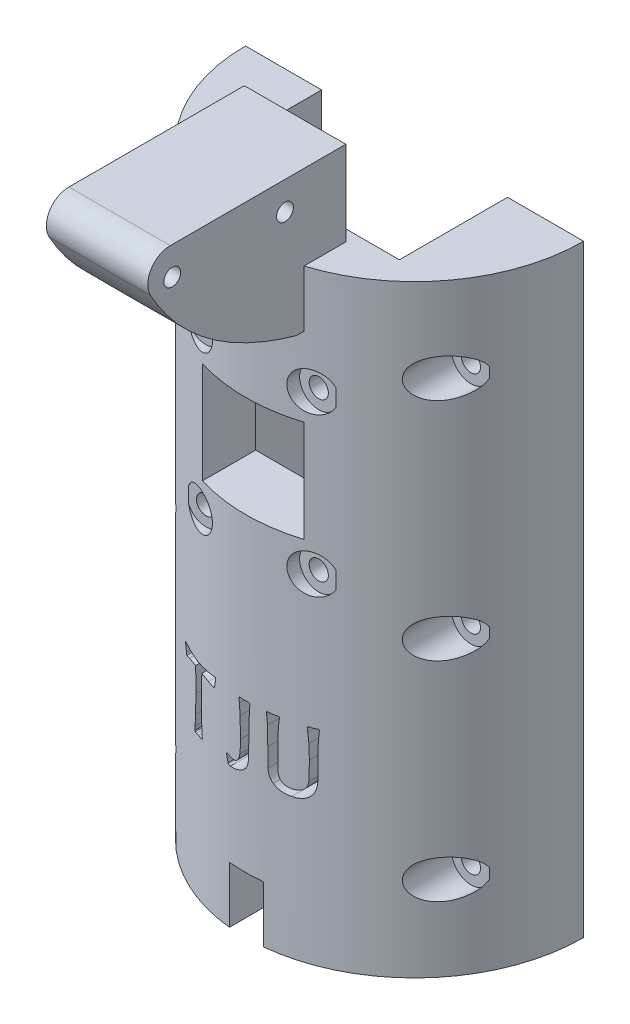
SolidWorks part; units mm, degrees
ref_plane "前视基准面" through (0, 0, 0) normal (0, 0, 1) x (1, 0, 0)
ref_plane "上视基准面" through (0, 0, 0) normal (0, 1, 0) x (1, 0, 0)
ref_plane "右视基准面" through (0, 0, 0) normal (1, 0, 0) x (0, 0, -1)
sketch "草图1" plane through (0, 0, 0) normal (0, 1, 0) x (1, 0, 0)
  line L0 (-30, 0) -> (30, 0)
  line L6 (15, 19.2) -> (-15, 19.2)
  line L7 (15, 19.2) -> (15, -19.2)
  line L8 (15, -19.2) -> (-15, -19.2)
  line L9 (-15, 19.2) -> (-15, -19.2)
  line L10 (15, 19.2) -> (-15, -19.2) construction
  line L11 (15, -19.2) -> (-15, 19.2) construction
  arc A0 (-30, 0) -> (30, 0) centre (0, 0) ccw
  point P0 (0, 0)
  dimension "D3" = 38.4
  dimension "D1" = 30
  dimension "D2" = 60
extrude "凸台-拉伸1" add sketch "草图1" along normal blind 80 contours L0 A0 L8 region at (-22.5, 0, 0.6708)
sketch "草图2" plane through (0, 0, 0) normal (0, 0, 1) x (1, 0, 0)
  line L0 (0, 122.0673) -> (0, -16.729) construction
  line L2 (-30, 0) -> (-15, 0) construction
  circle A0 centre (-10, 33) radius 1.7
  circle A1 centre (-10, 61) radius 1.7
  circle A2 centre (10, 33) radius 1.7
  circle A3 centre (10, 61) radius 1.7
  dimension "D1" = 20
  dimension "D2" = 20
  dimension "D3" = 33
  dimension "D4" = 28
extrude "切除-拉伸1" cut sketch "草图2" along normal blind 100
sketch "草图3" plane through (0, 0, 0) normal (0, 0, -1) x (-1, 0, 0)
  line L0 (-40.9161, 45) -> (57.667, 45) construction
  line L1 (-30, 80) -> (-30, 0) construction
  line L2 (30, 80) -> (30, 0) construction
  line L4 (-15, 80) -> (-30, 80) construction
  circle A0 centre (23.5, 65) radius 1.7
  circle A1 centre (-23.5, 65) radius 1.7
  circle A2 centre (23.5, 25) radius 1.7
  circle A3 centre (-23.5, 25) radius 1.7
  dimension "D1" = 40
  dimension "D2" = 40
  dimension "D3" = 6.5
  dimension "D4" = 6.5
  dimension "D5" = 15
extrude "切除-拉伸2" cut sketch "草图3" against normal blind 100
ref_plane "基准面1" through (0, 0, 40) normal (0, 0, -1) x (-1, 0, 0)
sketch "草图4" plane through (0, 0, 40) normal (0, 0, -1) x (-1, 0, 0)
  circle A0 centre (-23.5, 65) radius 3.4
  circle A1 centre (-23.5, 25) radius 3.4
  circle A2 centre (23.5, 65) radius 3.4
  circle A3 centre (23.5, 25) radius 3.4
extrude "切除-拉伸3" cut sketch "草图4" along normal blind 26.5
sketch "草图5" plane through (0, 0, 40) normal (0, 0, -1) x (-1, 0, 0)
  circle A0 centre (-10, 61) radius 3.4
  circle A1 centre (10, 61) radius 3.4
  circle A2 centre (-10, 33) radius 3.4
  circle A3 centre (10, 33) radius 3.4
extrude "切除-拉伸4" cut sketch "草图5" along normal blind 13 contours A2 | A3 | A1 | A0 region at (10, 61, 40) region at (-10, 61, 40) region at (10, 33, 40) region at (-10, 33, 40)
sketch "草图6" plane through (0, 0, 0) normal (0, -1, 0) x (1, 0, 0)
  line L0 (-30, 0) -> (30, 0)
  arc A0 (30, 0) -> (-30, 0) centre (0, 0) ccw
extrude "凸台-拉伸2" add sketch "草图6" along normal blind 3
sketch "草图7" plane through (0, -3, 0) normal (0, -1, 0) x (1, 0, 0)
  line L0 (-30, 0) -> (30, 0) construction
  line L1 (-6, 0) -> (6, 0)
  arc A0 (6, 0) -> (-6, 0) centre (0, 0) ccw
  dimension "D1" = 6
extrude "凸台-拉伸3" [suppressed] add sketch "草图7" along normal blind 9.5
sketch "草图8" plane through (0, 80, 0) normal (0, 1, 0) x (1, 0, 0)
  line L0 (0, 0) -> (0, -36.28) construction
  line L1 (-15, 0) -> (15, 0) construction
  line L2 (-7, -19.2) -> (7, -19.2)
  line L3 (15, -19.2) -> (-15, -19.2) construction
  line L4 (7, -19.2) -> (7, -29.1719)
  line L5 (-7, -19.2) -> (-7, -29.1719)
  arc A0 (-30, 0) -> (30, 0) centre (0, 0) ccw construction
  arc A1 (-7, -29.1719) -> (7, -29.1719) centre (0, 0) ccw
  point P8 (0, -19.2)
  dimension "D1" = 14
ref_plane "基准面2" through (0, 100, 0) normal (0, 1, 0) x (1, 0, 0)
sketch "草图9" plane through (0, 100, 0) normal (0, 1, 0) x (1, 0, 0)
  line L0 (0, 0) -> (0, -36.28) construction
  line L2 (-7, -19.2) -> (7, -19.2)
  line L3 (-7, -19.2) -> (-7, -64.2)
  line L4 (-7, -64.2) -> (7, -64.2)
  line L5 (7, -19.2) -> (7, -64.2)
  dimension "D1" = 14
  dimension "D2" = 45
ref_plane "基准面3" through (0, 70, 0) normal (0, 1, 0) x (1, 0, 0)
sketch "草图10" plane through (0, 70, 0) normal (0, 1, 0) x (1, 0, 0)
  line L0 (-15, 0) -> (15, 0) construction
  line L1 (-7, -29.1719) -> (-7, -19.2)
  line L2 (-7, -19.2) -> (7, -19.2)
  line L3 (7, -19.2) -> (7, -29.1719)
  arc A0 (-7, -29.1719) -> (7, -29.1719) centre (0, 0) ccw
sketch "草图13" plane through (0, 0, 0) normal (1, 0, 0) x (0, 0, -1)
  line L0 (-19.2, 100) -> (-60, 100)
  line L1 (-19.2, 100) -> (-64.2, 100) construction
  line L2 (-19.2, 100) -> (-64.2, 100) construction
  line L3 (-19.2, 100) -> (-19.2, 70)
  line L4 (-19.2, 70) -> (-29.1719, 70) construction
  line L5 (-29.1719, 70) -> (-19.2, 70) construction
  line L6 (-19.2, 70) -> (-30, 70)
  line L7 (-29.1719, 70) -> (-30, 70) construction
  line L8 (-30, 80) -> (-30, -3) construction
  line L9 (0, 80) -> (0, 0) construction
  spline S0 degree 2 poles (-60, 100) (-54.4581, 76.8596) (-30, 70) knots 0 0 0 1 1 1
  dimension "D1" = 19.2
extrude "凸台-拉伸4" add sketch "草图13" along normal mid plane 18
sketch "草图14" plane through (-9, 0, 0) normal (-1, 0, 0) x (0, 0, 1)
  line L0 (0, 80) -> (0, -3) construction
  line L1 (19.2, 100) -> (60, 100) construction
  circle A0 centre (32, 90) radius 1.5
  circle A1 centre (52, 90) radius 1.5
  dimension "D1" = 20
  dimension "D2" = 32
  dimension "D3" = 10
  dimension "D4" = 10
extrude "切除-拉伸6" cut sketch "草图14" against normal blind 18
sketch "草图17" plane through (0, 0, 0) normal (1, 0, 0) x (0, 0, -1)
  line L0 (0, 80) -> (0, -3) construction
  line L1 (-30, -3) -> (0, -3) construction
  circle A0 centre (0, 29) radius 3
  circle A1 centre (0, 49) radius 3
  dimension "D1" = 6
  dimension "D2" = 32
  dimension "D3" = 2
sketch "草图18" plane through (0, 100, 0) normal (0, 1, 0) x (1, 0, 0)
  line L0 (9, -19.2) -> (9, -60) construction
  line L1 (-9, -19.2) -> (9, -19.2)
  line L2 (-9, -19.2) -> (-9, -21.2)
  line L3 (-9, -21.2) -> (9, -21.2)
  line L4 (9, -19.2) -> (9, -21.2)
  dimension "D1" = 2
extrude "切除-拉伸9" cut sketch "草图18" against normal blind 20
sketch "草图19" plane through (0, 0, 0) normal (0, 1, 0) x (1, 0, 0)
  circle A0 centre (0, 0) radius 3
extrude "切除-拉伸10" [suppressed] cut sketch "草图19" against normal blind 3
ref_plane "基准面4" through (0, 16, 0) normal (0, 1, 0) x (1, 0, 0)
fillet "圆角4" [suppressed] radius 1
chamfer "倒角2" [suppressed] distance 2 angle 45
sketch "草图20" plane through (0, -3, 0) normal (0, -1, 0) x (1, 0, 0)
  line L0 (-30, 0) -> (30, 0) construction
  circle A0 centre (0, 20.5) radius 6
  dimension "D1" = 12
  dimension "D2" = 20.5
extrude "切除-拉伸11" [suppressed] cut sketch "草图20" against normal blind 15
sketch "草图23" [suppressed] plane through (0, 0, 19.2) normal (0, 0, -1) x (-1, 0, 0)
  line L1 (-5.8575, 12) -> (2.8125, 12)
  line L2 (-5.8575, 12) -> (-5.8575, -3.4639)
  line L3 (-5.8575, -3.4639) -> (2.8125, -3.4639)
  line L4 (2.8125, 12) -> (2.8125, -3.4639)
extrude "切除-拉伸14" [suppressed] cut sketch "草图23" against normal blind 30
sketch "草图25" plane through (0, 100, 0) normal (0, 1, 0) x (1, 0, 0)
  line L1 (-9, -21.2) -> (9, -21.2)
  line L2 (-9, -21.2) -> (-9, -60)
  line L3 (-9, -60) -> (9, -60)
  line L4 (9, -21.2) -> (9, -60)
extrude "切除-拉伸16" cut sketch "草图25" against normal blind 5
fillet "圆角6" radius 4 1 edges at (0, 95, 58.5139)
sketch "草图28" plane through (0, -3, 0) normal (0, -1, 0) x (1, 0, 0)
  line L5 (-30, 0) -> (30, 0)
  line L8 (-30, 0) -> (30, 0)
  arc A4 (30, 0) -> (-30, 0) centre (0, 0) ccw
  arc A7 (30, 0) -> (-30, 0) centre (0, 0) ccw
  dimension "D1" = 0
extrude "凸台-拉伸7" add sketch "草图28" along normal blind 19
sketch "草图26" [suppressed] plane through (0, -3, 0) normal (0, -1, 0) x (1, 0, 0)
  line L0 (-2.8125, 25.8) -> (-2.8125, 29.8679)
  line L1 (5.8575, 29.4226) -> (5.8575, 21.8)
  line L2 (-30, 0) -> (30, 0)
  arc A2 (-2.8125, 25.8) -> (5.8575, 21.8) centre (0, 20.5) ccw
  arc A3 (6, 0) -> (-6, 0) centre (0, 0) ccw
  arc A4 (30, 0) -> (-30, 0) centre (0, 0) ccw
extrude "凸台-拉伸5" [suppressed] add sketch "草图26" along normal blind 2
sketch "草图27" [suppressed] plane through (0, -12.5, 0) normal (0, -1, 0) x (1, 0, 0)
  line L0 (-6, 0) -> (6, 0)
  arc A0 (6, 0) -> (-6, 0) centre (0, 0) ccw
extrude "凸台-拉伸6" [suppressed] add sketch "草图27" along normal blind 2
sketch "草图29" plane through (0, 0, 0) normal (0, 1, 0) x (1, 0, 0)
  line L1 (15, -19.2) -> (-15, -19.2)
  line L2 (15, -19.2) -> (15, 0)
  line L3 (15, 0) -> (-15, 0)
  line L4 (-15, -19.2) -> (-15, 0)
extrude "切除-拉伸17" cut sketch "草图29" against normal up to next
sketch "草图30" plane through (0, -22, 0) normal (0, -1, 0) x (1, 0, 0)
  line L0 (30, 0) -> (-30, 0)
  line L5 (15, 19.2) -> (15, 0)
  line L6 (15, 0) -> (30, 0)
  line L7 (-30, 0) -> (-15, 0)
  line L8 (-15, 0) -> (-15, 19.2)
  line L9 (-15, 19.2) -> (15, 19.2)
  arc A1 (30, 0) -> (-30, 0) centre (0, 0) ccw
  arc A2 (30, 0) -> (-30, 0) centre (0, 0) ccw
  dimension "D1" = 0
extrude "凸台-拉伸9" add sketch "草图30" along normal blind 5
sketch "草图31" plane through (0, -22, 0) normal (0, 1, 0) x (1, 0, 0)
  line L0 (-15, 0) -> (15, 0) construction
  circle A0 centre (0, 0) radius 3
  dimension "D1" = 6
extrude "切除-拉伸18" cut sketch "草图31" against normal blind 3
fillet "圆角7" radius 1 1 edges at (0, -25, 3)
chamfer "倒角3" distance 2 angle 45 1 edges at (0, -22, 3)
sketch "草图32" plane through (15, 0, 0) normal (-1, 0, 0) x (0, 0, 1)
  line L4 (0, 80) -> (0, -22)
  line L5 (0, -22) -> (19.2, -22)
  line L6 (19.2, -22) -> (19.2, 80)
  line L7 (19.2, 80) -> (0, 80)
  line L8 (0, 80) -> (0, -22)
  line L9 (0, -22) -> (19.2, -22)
  line L10 (19.2, -22) -> (19.2, 80)
  line L11 (19.2, 80) -> (0, 80)
  dimension "D1" = 0
extrude "切除-拉伸19" cut sketch "草图32" against normal blind 1.5
sketch "草图33" plane through (-15, 0, 0) normal (1, 0, 0) x (0, 0, -1)
  line L4 (-19.2, 80) -> (-19.2, -22)
  line L5 (-19.2, -22) -> (0, -22)
  line L6 (0, -22) -> (0, 80)
  line L7 (0, 80) -> (-19.2, 80)
  line L8 (-19.2, 80) -> (-19.2, -22)
  line L9 (-19.2, -22) -> (0, -22)
  line L10 (0, -22) -> (0, 80)
  line L11 (0, 80) -> (-19.2, 80)
  dimension "D1" = 0
extrude "切除-拉伸20" cut sketch "草图33" against normal blind 1.5
sketch "草图34" plane through (0, -27, 0) normal (0, -1, 0) x (1, 0, 0)
  line L0 (-6, 0) -> (6, 0)
  arc A0 (6, 0) -> (-6, 0) centre (0, 0) ccw
  dimension "D1" = 6
extrude "凸台-拉伸10" add sketch "草图34" along normal blind 9.5
sketch "草图35" plane through (0, -27, 0) normal (0, -1, 0) x (1, 0, 0)
  line L0 (-6, 0) -> (6, 0) construction
  circle A0 centre (0, 18.5) radius 5
  dimension "D1" = 10
  dimension "D2" = 18.5
extrude "切除-拉伸21" cut sketch "草图35" against normal blind 15
sketch "草图36" plane through (0, 0, 19.2) normal (0, 0, -1) x (-1, 0, 0)
  line L2 (-3, -27) -> (3, -27)
  line L4 (-3, -27) -> (-3, -17)
  line L5 (-3, -17) -> (3, -17)
  line L6 (3, -27) -> (3, -17)
  line L7 (0, -17) -> (0, -27) construction
  line L8 (-3, -27) -> (3, -27) construction
  point P2 (0, -27)
  dimension "D1" = 6
extrude "切除-拉伸22" cut sketch "草图36" against normal blind 15
sketch "草图39" plane through (0, 0, 0) normal (0, 0, -1) x (-1, 0, 0)
  line L0 (-30, 80) -> (-30, -27) construction
  line L4 (-6, -27) -> (-30, -27) construction
  line L5 (30, 80) -> (30, -27) construction
  line L6 (30, -27) -> (6, -27) construction
  circle A0 centre (-23.5, -12) radius 1.7
  circle A2 centre (23.5, -12) radius 1.7
  dimension "D3" = 3.4
  dimension "D5" = 3.4
  dimension "D1" = 6.5
  dimension "D2" = 15
  dimension "D4" = 6.5
  dimension "D6" = 15
extrude "切除-拉伸23" cut sketch "草图39" against normal through all
sketch "草图40" plane through (0, 0, 40) normal (0, 0, -1) x (-1, 0, 0)
  circle A0 centre (-23.5, -12) radius 3.4
  circle A1 centre (23.5, -12) radius 3.4
  dimension "D1" = 6.8
  dimension "D2" = 6.8
extrude "切除-拉伸25" cut sketch "草图40" along normal blind 26.5
sketch "草图41" plane through (0, 0, 40) normal (0, 0, -1) x (-1, 0, 0)
  line L0 (0, 0) -> (0, 67.5936) construction
  line L1 (-9, 80) -> (-30, 80) construction
  line L2 (9, 56) -> (-9, 56)
  line L3 (9, 56) -> (9, 38)
  line L4 (9, 38) -> (-9, 38)
  line L5 (-9, 56) -> (-9, 38)
  line L6 (0, 38) -> (0, 56) construction
  line L7 (9, 47) -> (-9, 47) construction
  point P3 (0, 47)
  dimension "D1" = 33
  dimension "D2" = 18
  dimension "D3" = 18
extrude "切除-拉伸26" cut sketch "草图41" along normal through all
sketch "草图43" plane through (0, 0, 40) normal (0, 0, -1) x (-1, 0, 0)
  text T0 "TJU" font "华康龙门石碑W9" height in points 44
extrude "切除-拉伸27" cut sketch "草图43" along normal through all
